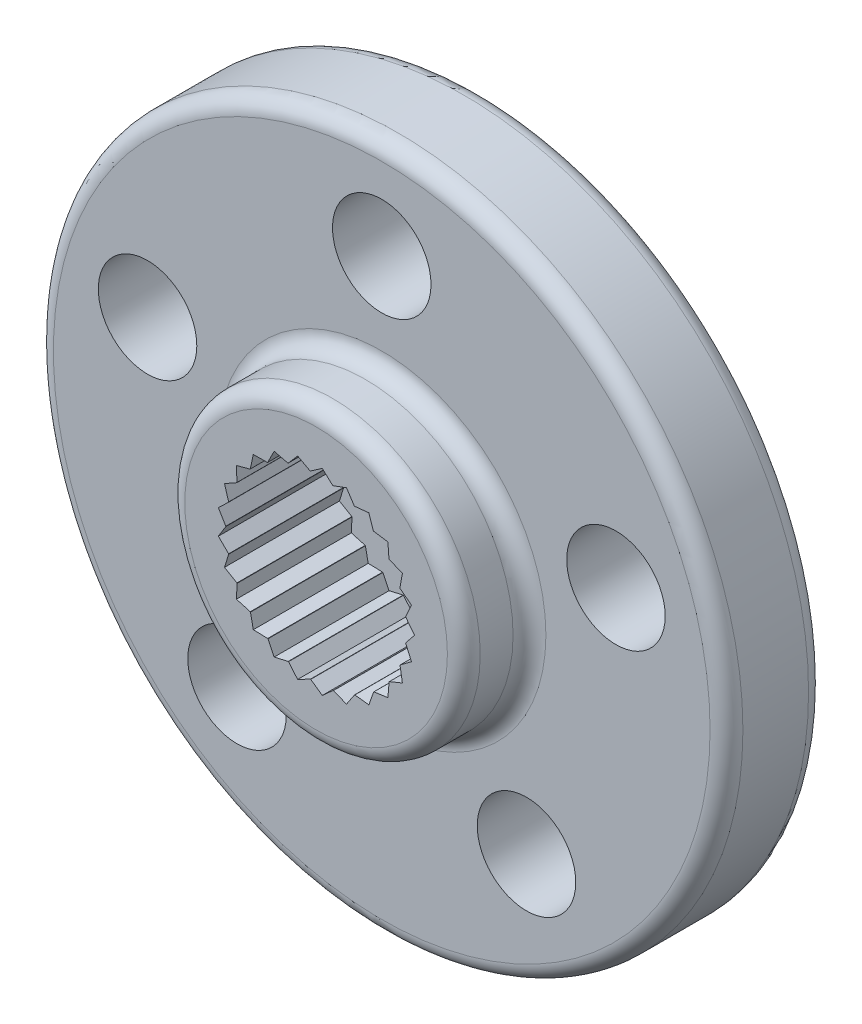
SolidWorks part; units mm, degrees
ref_plane "Front Plane" through (0, 0, 0) normal (0, 0, 1) x (1, 0, 0)
ref_plane "Top Plane" through (0, 0, 0) normal (0, 1, 0) x (1, 0, 0)
ref_plane "Right Plane" through (0, 0, 0) normal (1, 0, 0) x (0, 0, -1)
sketch "Sketch1" plane through (0, 0, 0) normal (0, 0, 1) x (1, 0, 0)
  line L0 (0, 0) -> (0, 7.5) construction
  circle A0 centre (0, 0) radius 10.5
  circle A6 centre (0, 0) radius 4.5
  circle A7 centre (0, 7.5) radius 1.5
  circle A8 centre (7.1329, 2.3176) radius 1.5
  circle A9 centre (4.4084, -6.0676) radius 1.5
  circle A10 centre (-4.4084, -6.0676) radius 1.5
  circle A11 centre (-7.1329, 2.3176) radius 1.5
  point P17 (0, 0)
  dimension "D1" = 21
  dimension "D2" = 3
  dimension "D4" = 5
  dimension "D3" = 7.5
extrude "Boss-Extrude1" add sketch "Sketch1" along normal blind 3
extrude "Boss-Extrude2" add sketch "Sketch1<2>" along normal blind 5 contours A6 region at (0, 0, 0)
sketch "Sketch1<2>" plane through (0, 0, 0) normal (0, 0, 1) x (1, 0, 0) same geometry as "Sketch1"
sketch "Sketch2" plane through (0, 0, 0) normal (0, 0, -1) x (-1, 0, 0)
  circle A0 centre (0, 0) radius 1.5
extrude "Cut-Extrude1" cut sketch "Sketch2" against normal blind 4.5
sketch "Sketch3" plane through (0, 0, 5) normal (0, 0, 1) x (1, 0, 0)
  circle A0 centre (0, 0) radius 2.75
extrude "Cut-Extrude2" cut sketch "Sketch3" against normal blind 3.5
sketch "Sketch4" plane through (0, 0, 5) normal (0, 0, 1) x (1, 0, 0)
  line L0 (0, 0) -> (-3, 0)
  line L1 (0, 0) -> (-2.9763, 0.376)
  line L2 (0, 0) -> (-2.9083, 0.7359)
  line L3 (-2.75, 0) -> (-2.9763, 0.376)
  line L4 (-2.666, 0.6746) -> (-2.9763, 0.376)
  circle A0 centre (0, 0) radius 3
  circle A1 centre (0, 0) radius 2.75 construction
  circle A2 centre (0, 0) radius 2.75 construction
  circle A3 centre (0, 0) radius 2.75
  circle M6 centre (0, 0) radius 2.75
  dimension "D1" = 7.2
  dimension "D2" = 14.2
extrude "Cut-Extrude3" cut sketch "Sketch4" against normal blind 3.5 contours L4 L1 M6 | L3 L1 M6 region at (-2.8205, 0.2422, 5) region at (-2.7928, 0.4638, 5)
pattern_circular "CirPattern1" count 25 over 360 about axis through (0, 0, 4.5) along (0, 0, -1) of "Cut-Extrude3" reverse direction yes
sketch "Sketch5" plane through (0, 0, 0) normal (0, 0, -1) x (-1, 0, 0)
  circle A0 centre (0, 0) radius 4.5
  circle A1 centre (0, 0) radius 2.5
  dimension "D1" = 5
extrude "Boss-Extrude3" add sketch "Sketch5" along normal blind 1
fillet "Fillet1" radius 0.5 1 edges at (-4.5, 0, -1)
fillet "Fillet2" radius 0.5 4 edges at (4.5, 0, 5) (10.5, 0, 3) (10.5, 0, 0) (4.5, 0, 3)
